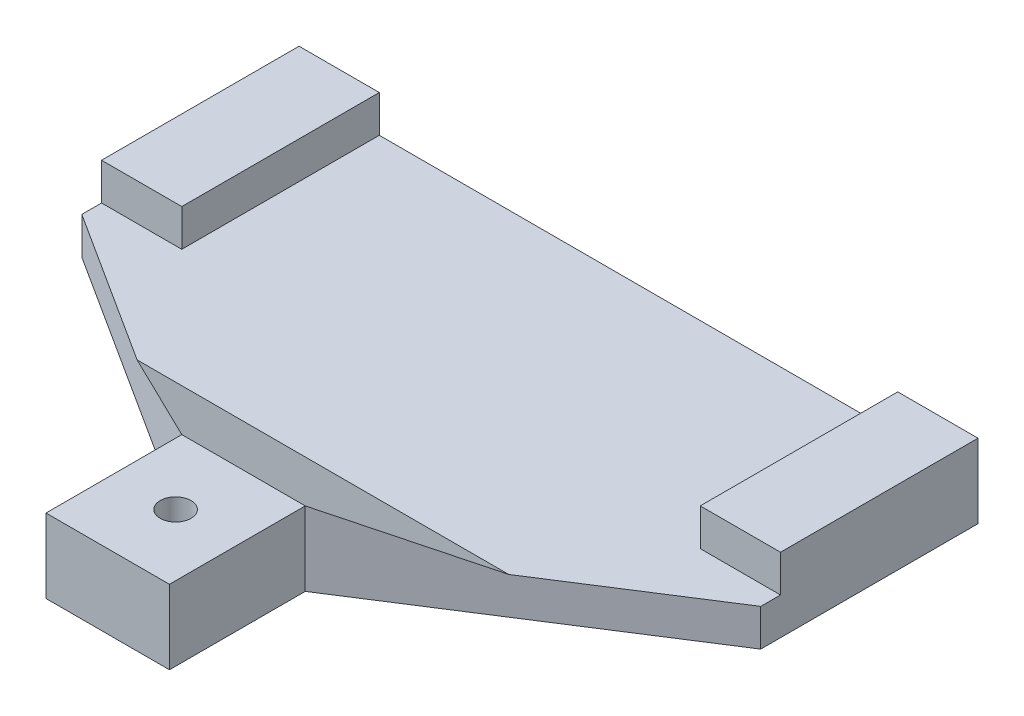
SolidWorks part; units mm, degrees
ref_plane "Plan de face" through (0, 0, 0) normal (0, 0, 1) x (1, 0, 0)
ref_plane "Plan de dessus" through (0, 0, 0) normal (0, 1, 0) x (1, 0, 0)
ref_plane "Plan de droite" through (0, 0, 0) normal (1, 0, 0) x (0, 0, -1)
sketch "Esquisse1" plane through (0, 0, 0) normal (0, 0, 1) x (1, 0, 0)
  line L1 (0, 0) -> (60, 0)
  line L2 (0, 0) -> (0, 6)
  line L3 (0, 6) -> (60, 6)
  line L4 (60, 0) -> (60, 6)
  dimension "D1" = 6
  dimension "D2" = 60
extrude "Boss.-Extru.1" add sketch "Esquisse1" along normal blind 60
sketch "Esquisse2" plane through (0, 0, 0) normal (0, 0, -1) x (-1, 0, 0)
  line L0 (-60, 6) -> (0, 6) construction
  line L1 (-60, 0) -> (-60, 6) construction
  line L2 (0, 6) -> (0, 0) construction
  circle A0 centre (-54, 3) radius 1.25
  circle A1 centre (-5.75, 3) radius 1.25
  dimension "D6" = 2.5
  dimension "D7" = 2.5
  dimension "D1" = 48.25
  dimension "D2" = 3
  dimension "D3" = 3
  dimension "D4" = 6
  dimension "D5" = 5.75
extrude "Enlèv. mat.-Extru.1" cut sketch "Esquisse2" against normal blind 15
sketch "Esquisse3" plane through (0, 6, 0) normal (0, 1, 0) x (1, 0, 0)
  line L0 (60, -60) -> (60, 0) construction
  line L1 (60, 0) -> (0, 0) construction
  circle A0 centre (30, -37.5) radius 1.25
  dimension "D1" = 2.5
  dimension "D2" = 30
  dimension "D3" = 37.5
extrude "Enlèv. mat.-Extru.2" cut sketch "Esquisse3" against normal blind 15
sketch "Esquisse4" plane through (0, 6, 0) normal (0, 1, 0) x (1, 0, 0)
  line L0 (0, -16) -> (9, -16)
  line L1 (0, -60) -> (0, 0) construction
  line L2 (9, -16) -> (9, 0)
  line L3 (60, 0) -> (0, 0) construction
  line L4 (9, 0) -> (51, 0)
  line L5 (51, 0) -> (51, -16)
  line L6 (51, -16) -> (60, -16)
  line L7 (60, -60) -> (60, 0) construction
  line L8 (60, -16) -> (60, -60)
  line L9 (60, -60) -> (0, -60)
  line L10 (0, -60) -> (0, -16)
  line L11 (25, -43) -> (35, -43)
  line L12 (35, -43) -> (35, -32)
  line L13 (35, -32) -> (25, -32)
  line L14 (25, -32) -> (25, -43)
  dimension "D1" = 9
  dimension "D2" = 9
  dimension "D3" = 16
  dimension "D4" = 16
  dimension "D5" = 17
  dimension "D6" = 32
  dimension "D7" = 25
  dimension "D8" = 25
extrude "Enlèv. mat.-Extru.3" cut sketch "Esquisse4" against normal blind 3
sketch "Esquisse5" plane through (0, 3, 0) normal (0, 1, 0) x (1, 0, 0)
  line L0 (60, -16) -> (35, -32)
  line L1 (35, -32) -> (35, -43)
  line L2 (35, -43) -> (25, -43)
  line L3 (25, -43) -> (25, -32)
  line L4 (25, -32) -> (0, -16)
  line L5 (0, -16) -> (-21.5949, -85.4755)
  line L6 (-21.5949, -85.4755) -> (75.4145, -69.9308)
  line L7 (75.4145, -69.9308) -> (60, -16)
extrude "Enlèv. mat.-Extru.4" cut sketch "Esquisse5" against normal blind 52
chamfer "Chanfrein1" distance 3 angle 65 1 edges at (30, 3, 32) first distance on face at (30, 4.5, 32)
sketch "Esquisse6" plane through (0, 0, 0) normal (0, 0, -1) x (-1, 0, 0)
  line L0 (0, 0) -> (-60, 0) construction
  line L1 (-60, 6) -> (-57.5, 6)
  line L2 (-60, 6) -> (-60, 0)
  line L3 (-60, 0) -> (-57.5, 0)
  line L4 (-57.5, 6) -> (-57.5, 0)
  line L5 (-9, 6) -> (0, 6) construction
  line L6 (0, 0) -> (-2.5, 0)
  line L7 (0, 0) -> (0, 6)
  line L8 (0, 6) -> (-2.5, 6)
  line L9 (-2.5, 0) -> (-2.5, 6)
  dimension "D1" = 2.5
  dimension "D2" = 2.5
extrude "Enlèv. mat.-Extru.5" cut sketch "Esquisse6" against normal blind 40
